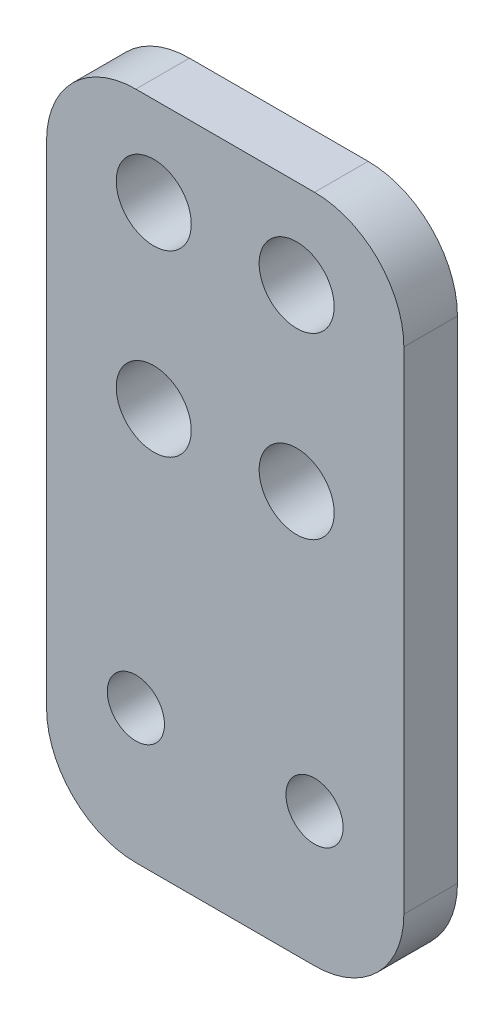
SolidWorks part; units mm, degrees
ref_plane "正面" through (0, 0, 0) normal (0, 0, 1) x (1, 0, 0)
ref_plane "平面" through (0, 0, 0) normal (0, 1, 0) x (1, 0, 0)
ref_plane "右側面" through (0, 0, 0) normal (1, 0, 0) x (0, 0, -1)
sketch "ｽｹｯﾁ2" plane through (0, 0, 0) normal (0, 0, 1) x (1, 0, 0)
  line L0 (0, 0) -> (0, -20) construction
  line L1 (-4, -5) -> (4, -5) construction
  line L2 (-4, -5) -> (-4, 5) construction
  line L3 (-4, 5) -> (4, 5) construction
  line L4 (4, -5) -> (4, 5) construction
  line L5 (-4, -5) -> (4, 5) construction
  line L6 (-4, 5) -> (4, -5) construction
  line L7 (5, -20) -> (-5, -20) construction
  line L8 (-10, -27.5) -> (10, -27.5)
  line L9 (-10, -27.5) -> (-10, 10)
  line L10 (-10, 10) -> (10, 10)
  line L11 (10, -27.5) -> (10, 10)
  line L12 (-10, -27.5) -> (10, 10) construction
  line L13 (-10, 10) -> (10, -27.5) construction
  circle A0 centre (-4, 5) radius 2.1
  circle A1 centre (-4, -5) radius 2.1
  circle A2 centre (4, -5) radius 2.1
  circle A3 centre (4, 5) radius 2.1
  circle A4 centre (0, -20) radius 1.6 construction
  circle A5 centre (5, -20) radius 1.6
  circle A6 centre (-5, -20) radius 1.6
  point P0 (0, 0)
  point P13 (0, -8.75)
  point P21 (0, -20)
  dimension "D1" = 4.2
  dimension "D4" = 3.2
  dimension "D5" = 15
  dimension "D9" = 10
  dimension "D2" = 10
  dimension "D3" = 8
  dimension "D6" = 20
  dimension "D7" = 7.5
  dimension "D8" = 5
extrude "ﾎﾞｽ - 押し出し1" add sketch "ｽｹｯﾁ2" along normal blind 3
fillet "ﾌｨﾚｯﾄ1" radius 5 4 edges at (-10, -27.5, 1.5) (10, -27.5, 1.5) (-10, 10, 1.5) (10, 10, 1.5)
